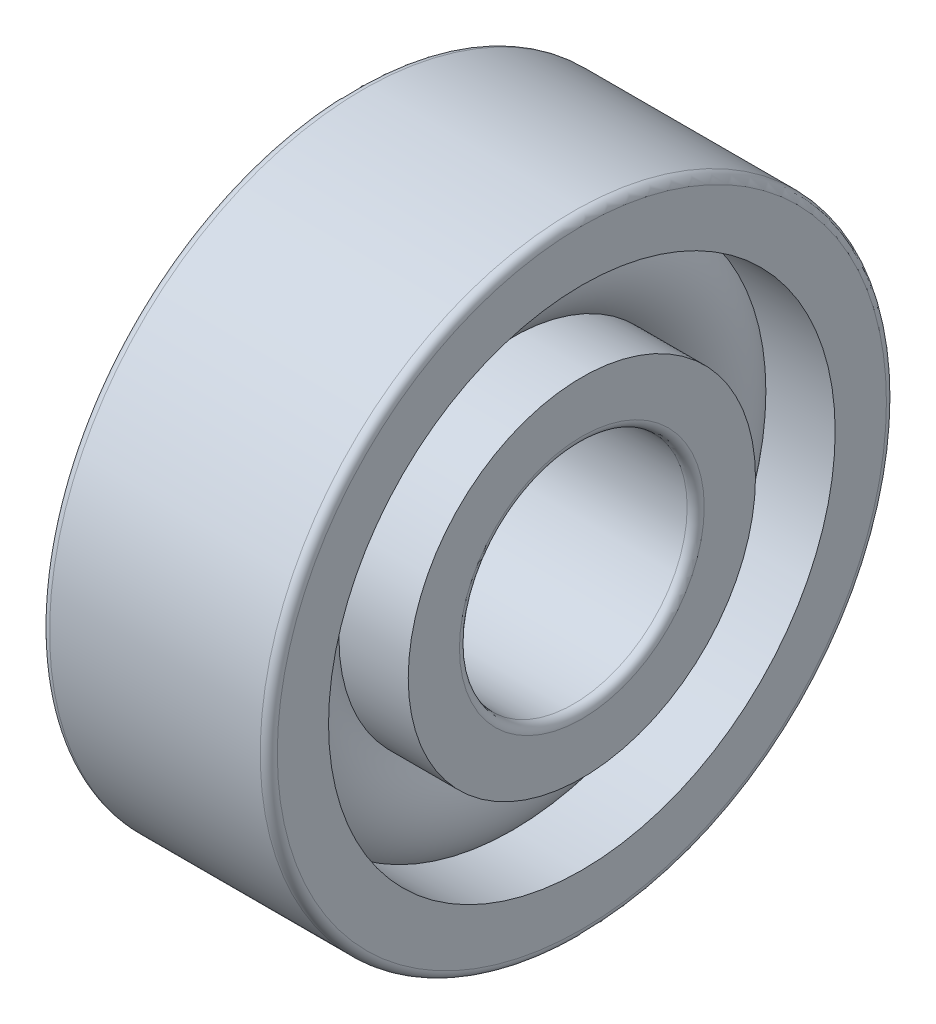
SolidWorks part; units mm, degrees
ref_plane "Plane1" through (0, 0, 0) normal (0, 0, 1) x (1, 0, 0)
ref_plane "Plane2" through (0, 0, 0) normal (0, 1, 0) x (1, 0, 0)
ref_plane "Plane3" through (0, 0, 0) normal (1, 0, 0) x (0, 0, -1)
other "Configuration Table"
sketch "Clipboard" plane through (0, 0, 0) normal (0, 0, 1) x (1, 0, 0)
  line L0 (-10, 0) -> (10, 0) construction
  line L1 (0, 0) -> (22.3471, -0.7804)
  line L2 (0, 0) -> (3.7477, 0.1309)
  line L3 (0, 0) -> (22.3471, -0.7804)
  line L4 (0, 0) -> (-22.3573, -0.3902)
  dimension "BallCLRad" = 3.75
sketch "CagSpiSke" plane through (0, 0, 0) normal (0, 0, 1) x (1, 0, 0)
  line L0 (0.105, 3.575) -> (0.105, 3.925)
  line L1 (0.105, 3.925) -> (-0.105, 3.925)
  line L2 (-0.105, 3.925) -> (-0.105, 3.575)
  line L3 (-0.105, 3.575) -> (0.105, 3.575)
  line L4 (-20.6375, 0) -> (20.6375, 0) construction
  line L5 (0, 0) -> (0, 23.7692) construction
  dimension "OD" = 7.85
  dimension "ID" = 7.15
revolve "CageSpine" add sketch "CagSpiSke" angle 0.001 about L4 reverse direction yes
ref_axis "Axis1" through (-50, 0, 0) along (1, 0, 0)
sketch "CagBalSke" plane through (0, 0, 0) normal (0, 0, 1) x (1, 0, 0)
  line L0 (-1.155, 3.75) -> (1.155, 3.75)
  line L1 (-1.905, 3.75) -> (1.905, 3.75) construction
  line L2 (-10, 0) -> (10, 0) construction
  line L3 (0, 0) -> (0, 24) construction
  arc A0 (1.155, 3.75) -> (-1.155, 3.75) centre (0, 3.75) cw
  dimension "BallCLRad" = 3.75
revolve "CageBall" [suppressed] add sketch "CagBalSke" angle 360 about L1 reverse direction yes
pattern_circular "CageBalls" [suppressed] count 2 every 180 about axis through (-50, 0, 0) along (1, 0, 0)
sketch "CagTrmODSke" plane through (0, 0, 0) normal (0, 0, 1) x (1, 0, 0)
  line L0 (1.156, 3.925) -> (1.156, 4.906)
  line L1 (1.156, 4.906) -> (-1.156, 4.906)
  line L2 (-1.156, 4.906) -> (-1.156, 3.925)
  line L3 (-1.156, 3.925) -> (1.156, 3.925)
  line L4 (-20.6375, 0) -> (20.6375, 0) construction
  line L5 (0, 0) -> (0, 25) construction
  dimension "Width" = 2.312
  dimension "ID" = 7.85
  dimension "OD" = 9.812
revolve "CageTrimOD" [suppressed] cut sketch "CagTrmODSke" angle 360 about L4 reverse direction yes
sketch "CagTrmIDSke" plane through (0, 0, 0) normal (0, 0, 1) x (1, 0, 0)
  line L0 (1.156, 2.596) -> (1.156, 3.575)
  line L1 (1.156, 3.575) -> (-1.156, 3.575)
  line L2 (-1.156, 3.575) -> (-1.156, 2.596)
  line L3 (-1.156, 2.596) -> (1.156, 2.596)
  line L4 (-20.6375, 0) -> (20.6375, 0) construction
  line L5 (0, 0) -> (0, 25) construction
  dimension "Width" = 2.312
  dimension "ID" = 5.192
  dimension "OD" = 7.15
revolve "CageTrimID" [suppressed] cut sketch "CagTrmIDSke" angle 360 about L4 reverse direction yes
sketch "BalSimSke" plane through (0, 0, 0) normal (0, 0, 1) x (1, 0, 0)
  line L0 (-10, 0) -> (10, 0) construction
  line L1 (-10, 3.75) -> (10, 3.75) construction
  line L2 (0, 0) -> (0, 23) construction
  circle A0 centre (0, 3.75) radius 1.05
  dimension "BallCLRad" = 3.75
  dimension "Ball_diameter" = 2.1
revolve "BallsSimplified" add sketch "BalSimSke" angle 360 about L0
sketch "BalDetSke" plane through (0, 0, 0) normal (0, 0, 1) x (1, 0, 0)
  line L0 (-1.05, 3.75) -> (1.05, 3.75)
  line L1 (-1.905, 3.75) -> (1.905, 3.75) construction
  line L2 (0, 0) -> (0, 25) construction
  arc A0 (1.05, 3.75) -> (-1.05, 3.75) centre (0, 3.75) cw
  dimension "BallCLRad" = 3.75
  dimension "Ball_diameter" = 2.1
revolve "BallDetailed" [suppressed] add sketch "BalDetSke" angle 360 about L1 reverse direction yes
sketch "InnRacSke" plane through (0, 0, 0) normal (0, 0, 1) x (1, 0, 0)
  line L0 (-0.7487, 3.05) -> (-2, 3.05)
  line L1 (-2, 3.05) -> (-2, 2.15)
  line L2 (-1.85, 2) -> (1.85, 2)
  line L3 (2, 2.15) -> (2, 3.05)
  line L4 (2, 3.05) -> (0.7487, 3.05)
  line L5 (-20.6375, 0) -> (20.6375, 0) construction
  line L6 (0, 0) -> (0, 30) construction
  arc A0 (-2, 2.15) -> (-1.85, 2) centre (-1.85, 2.15) ccw
  arc A1 (1.85, 2) -> (2, 2.15) centre (1.85, 2.15) ccw
  arc A2 (0.7487, 3.05) -> (-0.7487, 3.05) centre (0, 3.75) cw
  dimension "BallCLRad" = 3.75
  dimension "Fillet_radius" = 0.15
  dimension "Ball_diameter" = 2.05
  dimension "ID" = 4
  dimension "OD" = 6.1
  dimension "Width" = 4
revolve "InnerRace" add sketch "InnRacSke" angle 360 about L5 reverse direction yes
sketch "OutRacSke" plane through (0, 0, 0) normal (0, 0, 1) x (1, 0, 0)
  line L0 (-0.7487, 4.45) -> (-2, 4.45)
  line L1 (-2, 4.45) -> (-2, 5.35)
  line L2 (-1.85, 5.5) -> (1.85, 5.5)
  line L3 (2, 5.35) -> (2, 4.45)
  line L4 (2, 4.45) -> (0.7487, 4.45)
  line L5 (-20.6375, 0) -> (20.6375, 0) construction
  line L6 (0, 0) -> (0, 30) construction
  arc A0 (-2, 5.35) -> (-1.85, 5.5) centre (-1.85, 5.35) cw
  arc A1 (1.85, 5.5) -> (2, 5.35) centre (1.85, 5.35) cw
  arc A2 (0.7487, 4.45) -> (-0.7487, 4.45) centre (0, 3.75) ccw
  dimension "BallCLRad" = 3.75
  dimension "Fillet_radius" = 0.15
  dimension "Ball_diameter" = 2.05
  dimension "Width" = 4
revolve "OuterRace" add sketch "OutRacSke" angle 360 about L5 reverse direction yes
pattern_circular "BallsDetailed" [suppressed] count 2 every 180 about axis through (-50, 0, 0) along (1, 0, 0)
equation "\"BallCLRad@Clipboard\" = ( \"OD@OutRacSke\" + \"ID@InnRacSke\" ) / 4"
equation "\"BallCLRad@BalSimSke\" = \"BallCLRad@Clipboard\""
equation "\"BallCLRad@BalDetSke\" = \"BallCLRad@Clipboard\""
equation "\"BallCLRad@InnRacSke\" = \"BallCLRad@Clipboard\""
equation "\"BallCLRad@OutRacSke\" = \"BallCLRad@Clipboard\""
equation "\"Ball_diameter@InnRacSke\" = \"Ball_diameter@BalDetSke\" - 0.05"
equation "\"Ball_diameter@OutRacSke\" = \"Ball_diameter@BalDetSke\" - 0.05"
equation "\"Ball_diameter@BalSimSke\" = \"Ball_diameter@BalDetSke\""
equation "\"Width@OutRacSke\" = \"Width@InnRacSke\""
equation "\"Fillet_radius@OutRacSke\" = \"Fillet_radius@InnRacSke\""
equation "\"Max_count@Clipboard\" = int( 3.14159265 / atn(( \"Ball_diameter@BalDetSke\" / 2) / sqr( \"BallCLRad@Clipboard\"  *  \"BallCLRad@Clipboard\" - ( \"Ball_diameter@BalDetSke\" / 2) *  ( \"Ball_diameter@BalDetSke\" / 2))))"
equation "\"Max_count@Clipboard\" = ((sgn( \"Max_count@Clipboard\" - \"Count@Clipboard\" )-1)*( \"Max_count@Clipboard\" - \"Count@Clipboard\" ))/-2+ \"Count@Clipboard\""
equation "\"Count@BallsDetailed\" = int( \"Show_count@Clipboard\" ) "
equation "\"Count@BallsDetailed\" = ((sgn( \"Count@BallsDetailed\" - \"Max_count@Clipboard\" )-1)*( \"Count@BallsDetailed\" - \"Max_count@Clipboard\" ))/-2+ \"Max_count@Clipboard\""
equation "\"Count@BallsDetailed\" = ((sgn( \"Count@BallsDetailed\" - \"Min_count@Clipboard\" )+1)*( \"Count@BallsDetailed\" - \"Min_count@Clipboard\"))/2 +\"Min_count@Clipboard\""
equation "\"Angle@BallsDetailed\" = 360.0 / \"Max_count@Clipboard\""
equation "\"BallCLRad@CagBalSke\" = \"BallCLRad@Clipboard\""
equation "\"Count@CageBalls\" = \"Count@BallsDetailed\""
equation "\"Angle@CageBalls\" = \"Angle@BallsDetailed\""
equation "\"Angle@CageSpine\" =  \"Angle@CageBalls\" * ( \"Count@CageBalls\" -1 + int( \"Count@CageBalls\" / \"Max_count@Clipboard\" ) )  + 0.001 -  int( \"Count@CageBalls\" / \"Max_count@Clipboard\" ) * 0.001"
equation "\"Angle@CageSpine\" =  \"Angle@CageSpine\" * int( \"Min_count@Clipboard\" / 2) + int(1 / \"Min_count@Clipboard\")  * 0.001"
equation "\"CageWallOD@CagBalSke\" =  \"Ball_diameter@BalDetSke\" * 1.1"
equation "\"Thickness@CagSpiSke\" =  \"Ball_diameter@BalDetSke\" * 0.1"
equation "\"OD@CagTrmODSke\" = \"BallCLRad@Clipboard\" * 2 + \"CageWallOD@CagBalSke\" + 0.002"
equation "\"ID@CagTrmODSke\" = \"BallCLRad@Clipboard\" * 2 + \"Ball_diameter@BalDetSke\" / 6"
equation "\"OD@CagTrmIDSke\" = \"BallCLRad@Clipboard\" * 2 - \"Ball_diameter@BalDetSke\" / 6"
equation "\"ID@CagTrmIDSke\" = \"BallCLRad@Clipboard\" * 2 - \"CageWallOD@CagBalSke\" + 0.002"
equation "\"OD@CagSpiSke\" = \"ID@CagTrmODSke\""
equation "\"ID@CagSpiSke\" = \"OD@CagTrmIDSke\""
equation "\"Width@CagTrmODSke\" = \"CageWallOD@CagBalSke\" + 0.002"
equation "\"Width@CagTrmIDSke\" = \"CageWallOD@CagBalSke\" + 0.002"
